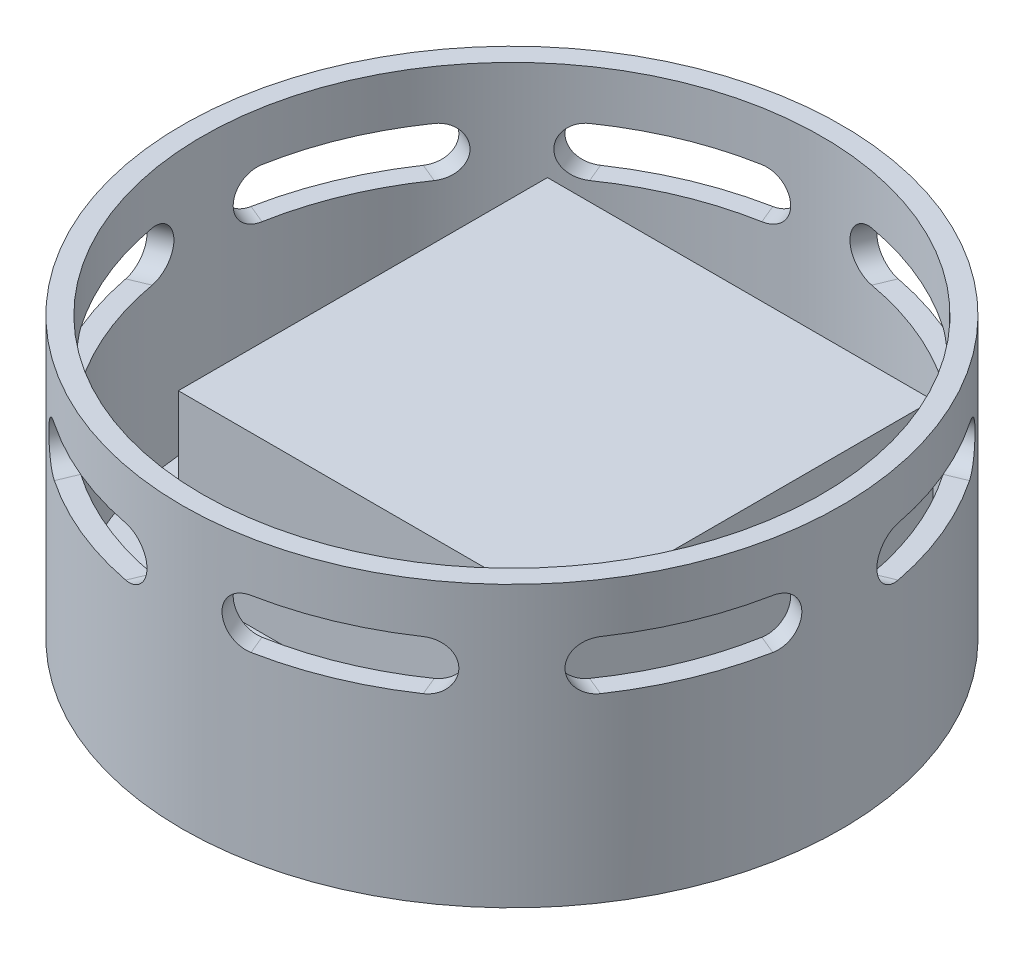
SolidWorks part; units mm, degrees
ref_plane "Front Plane" through (0, 0, 0) normal (0, 0, 1) x (1, 0, 0)
ref_plane "Top Plane" through (0, 0, 0) normal (0, 1, 0) x (1, 0, 0)
ref_plane "Right Plane" through (0, 0, 0) normal (1, 0, 0) x (0, 0, -1)
sketch "Sketch1" plane through (0, 0, 0) normal (0, 1, 0) x (1, 0, 0)
  circle A0 centre (0, 0) radius 100
  circle A1 centre (0, 0) radius 94
extrude "Boss-Extrude1" add sketch "Sketch1" along normal blind 5 contours A1 region at (0, 0, 0)
extrude "Boss-Extrude2" add sketch "Sketch1<3>" along normal blind 85 contours A0 A1 region at (-97.1716, 0, 0)
sketch "Sketch1<3>" plane through (0, 0, 0) normal (0, 1, 0) x (1, 0, 0) same geometry as "Sketch1"
ref_axis "Axis1" through (0, 85, 0) along (0, -1, 0)
ref_plane "Plane1" through (0, 0, 0) normal (-0.3827, 0, 0.9239) x (0, -1, 0)
sketch "Sketch4" plane through (0, 0, 0) normal (-0.3827, 0, 0.9239) x (0.9239, 0, 0.3827)
  line L0 (0, 0) -> (0, 62.5)
  line L1 (-20, 62.5) -> (20, 62.5) construction
  line L2 (-20, 70) -> (20, 70)
  line L3 (-20, 55) -> (20, 55)
  arc A0 (-20, 70) -> (-20, 55) centre (-20, 62.5) ccw
  arc A1 (20, 55) -> (20, 70) centre (20, 62.5) ccw
  point P5 (0, 62.5)
extrude "Cut-Extrude1" cut sketch "Sketch4" along normal up to surface (97.9796 mm away) contours L3 A1 L2 A0 region at (0, 69.4299, 0) up to face at (0, 85, 100)
pattern_circular "CirPattern1" count 8 over 360 about axis through (0, 85, 0) along (0, -1, 0) of "Cut-Extrude1"
sketch "Sketch2" plane through (0, 5, 0) normal (0, 1, 0) x (1, 0, 0)
  line L0 (-59.7991, -41.4218) -> (57.2009, -41.4218)
  line L1 (-59.7991, -41.4218) -> (-59.7991, 70.5782)
  line L2 (57.2009, -41.4218) -> (57.2009, 70.5782)
  line L3 (-59.7991, 70.5782) -> (57.2009, 70.5782)
extrude "Boss-Extrude6" add sketch "Sketch2" along normal blind 51
sketch "Sketch3" plane through (0, 0, 41.4218) normal (0, 0, 1) x (1, 0, 0)
  line L0 (-59.7991, 56) -> (-59.7991, 50)
  line L1 (-59.7991, 56) -> (57.2009, 56)
  line L2 (-59.7991, 50) -> (57.2009, 50)
  line L3 (57.2009, 56) -> (57.2009, 50)
  line L4 (-59.7991, 56) -> (-59.7991, 5) construction
  line L5 (57.2009, 56) -> (57.2009, 5) construction
  line L6 (-59.7991, 50) -> (-59.7991, 41)
  line L7 (-59.7991, 50) -> (57.2009, 50)
  line L8 (-59.7991, 41) -> (57.2009, 41)
  line L9 (57.2009, 50) -> (57.2009, 41)
  line L11 (-59.7991, 41) -> (57.2009, 41)
